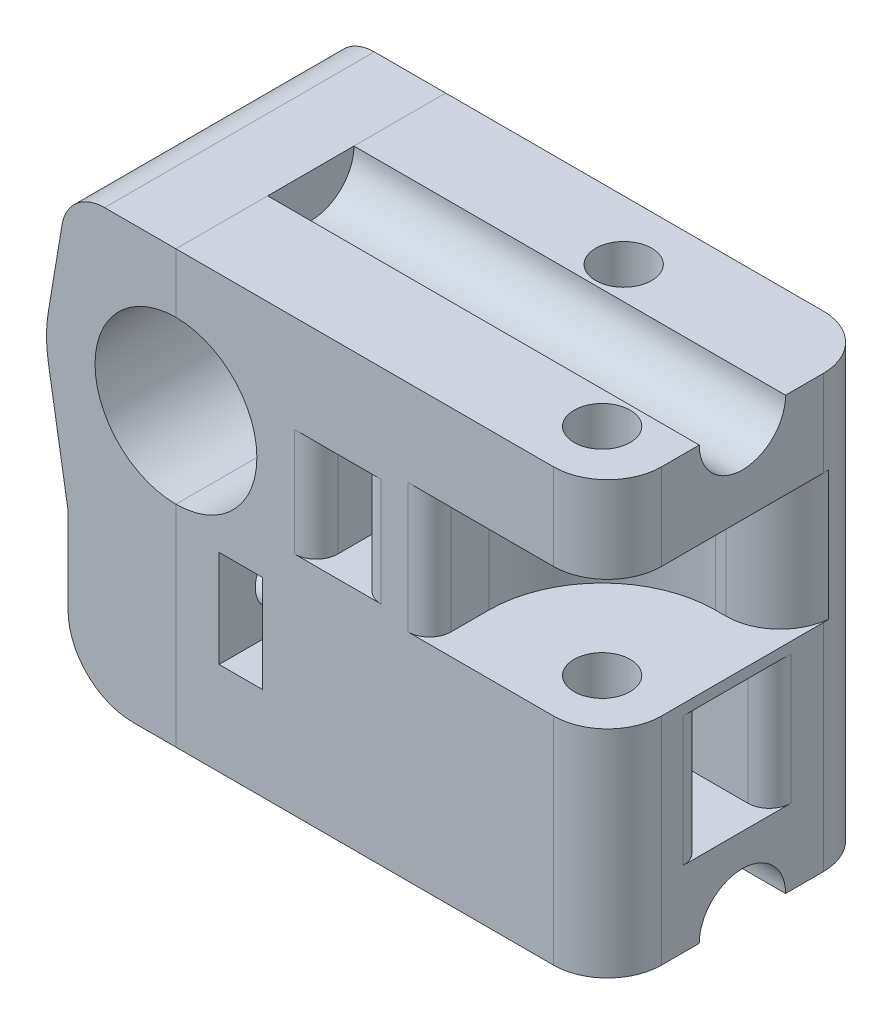
SolidWorks part; units mm, degrees
ref_plane "Front Plane" through (0, 0, 0) normal (0, 0, 1) x (1, 0, 0)
ref_plane "Top Plane" through (0, 0, 0) normal (0, 1, 0) x (1, 0, 0)
ref_plane "Right Plane" through (0, 0, 0) normal (1, 0, 0) x (0, 0, -1)
sketch "Sketch1" plane through (0, 0, 0) normal (0, 0, 1) x (1, 0, 0)
  line L0 (-15, 7) -> (-15, 0) construction
  line L1 (25, -20) -> (-25, -20)
  line L2 (25, -20) -> (25, 20)
  line L3 (25, 20) -> (-25, 20)
  line L4 (-25, -20) -> (-25, 20)
  line L5 (25, -20) -> (-25, 20) construction
  line L6 (25, 20) -> (-25, -20) construction
  line L7 (-15, 0) -> (0, 0) construction
  line L8 (-15, 7) -> (-15, -8) construction
  line L9 (-15, -8) -> (12.294, -8) construction
  line L10 (12.294, -8) -> (12.294, 8) construction
  line L11 (0, 0) -> (12.294, 0) construction
  circle A2 centre (-15, 7) radius 7.5
  point P0 (0, 0)
  dimension "D2" = 10
  dimension "D3" = 50
  dimension "D5" = 15
  dimension "D4" = 40
  dimension "D6" = 16
extrude "Boss-Extrude1" add sketch "Sketch1" along normal blind 25 contours A2 L3 L4 L1 L2 region at (1.4538, -0.6784, 0)
sketch "Sketch2" plane through (25, 0, 0) normal (1, 0, 0) x (0, 0, -1)
  line L0 (-25, 20) -> (0, -20) construction
  line L1 (-12.5, 20) -> (-12.5, -20) construction
  line L2 (-25, 20) -> (0, 20) construction
  circle A0 centre (-12.5, 20) radius 4
  circle A1 centre (-12.5, -20) radius 4
  point P7 (-12.5, 0)
  dimension "D2" = 8
extrude "Cut-Extrude1" cut sketch "Sketch2" against normal offset from surface (40 mm away) 10 up to face at (-25, 0, 12.5)
sketch "Sketch4" plane through (0, 20, 0) normal (0, 1, 0) x (1, 0, 0)
  line L0 (-15, -12.5) -> (13, -12.5) construction
  line L1 (19, -19.5) -> (7, -19.5) construction
  line L2 (19, -19.5) -> (19, -5.5) construction
  line L3 (19, -5.5) -> (7, -5.5) construction
  line L4 (7, -19.5) -> (7, -5.5) construction
  line L5 (19, -19.5) -> (7, -5.5) construction
  line L6 (19, -5.5) -> (7, -19.5) construction
  line L7 (-15, -8.5) -> (-15, -16.5) construction
  line L9 (-5.4237, 0) -> (-5.4237, -25)
  line L17 (-25, -25) -> (-25, 0) construction
  circle A0 centre (19, -19.5) radius 2.6
  circle A1 centre (7, -5.5) radius 2.6
  point P0 (13, -12.5)
  dimension "D3" = 5.2
  dimension "D1" = 12
  dimension "D2" = 14
  dimension "D4" = 32
extrude "Cut-Extrude2" cut sketch "Sketch4" against normal through all contours A1 | A0 region at (19, 20, 19.5) region at (7, 20, 5.5)
sketch "Sketch17" plane through (0, 0, 0) normal (0, 0, -1) x (-1, 0, 0)
  line L0 (25, -20) -> (25, 20) construction
  line L1 (25, 20) -> (26.8369, 8.9716)
  line L2 (25, -6) -> (26.8369, 5.0284)
  line L3 (25, 20) -> (25, -6)
  circle A0 centre (15, 7) radius 12
  point P3 (27, 7)
  line M12 (25, -20) -> (25, 20)
  dimension "D1" = 2
extrude "Boss-Extrude2" add sketch "Sketch17" against normal up to surface (25 mm away) contours A0 L2 M12 | A0 L3 | A0 L1 M12 region at (-25.5401, 14.7119, 0) region at (-25.806, 7, 0) region at (-25.5401, -0.7119, 0) up to face at (-7.5, 7, 25)
sketch "Sketch7" plane through (0, 20, 0) normal (0, 1, 0) x (1, 0, 0)
  line L0 (9, 14) -> (9, -25)
  line L2 (21, -39) -> (21, 0)
  point P6 (9, -5.5)
  point P12 (21, -19.5)
sketch "Sketch6" plane through (0, 0, 25) normal (0, 0, 1) x (1, 0, 0)
  line L0 (9.6, 20) -> (4.4, 20) construction
  line L1 (-2, 11) -> (2, 11)
  line L2 (-2, 11) -> (-2, 1)
  line L3 (-2, 1) -> (2, 1)
  line L4 (2, 11) -> (2, 1)
  line L5 (-2, 11) -> (2, 1) construction
  line L6 (-2, 1) -> (2, 11) construction
  point P0 (0, 6)
  point P5 (0, 0)
  point P6 (9, 20)
  dimension "D1" = 11
  dimension "D2" = 4
  dimension "D3" = 10
  dimension "D4" = 7
extrude "Cut-Extrude3" cut sketch "Sketch6" against normal through all
sketch "Sketch8" plane through (0, 20, 0) normal (0, 1, 0) x (1, 0, 0)
  line L0 (19, -9) -> (29.5, -9)
  line L1 (29.5, -9) -> (29.5, -30)
  line L2 (29.5, -30) -> (19, -30)
  line L3 (8.5, -19.5) -> (8.5, -30)
  line L4 (8.5, -30) -> (19, -30)
  arc A0 (19, -9) -> (8.5, -19.5) centre (19, -19.5) ccw
  dimension "D1" = 21
extrude "Cut-Extrude4" cut sketch "Sketch8" against normal blind 12 from offset 8 offset against normal yes
sketch "Sketch11" plane through (0, 20, 0) normal (0, 1, 0) x (1, 0, 0)
  line L1 (16, -5) -> (16, -10)
  line L2 (7, -16) -> (26.2266, -16)
  line L4 (16, -10) -> (26.2266, -10)
  line L5 (26.2266, -16) -> (26.2266, -10)
  line L7 (-3.5, -5.5) -> (-3.5, 3.5)
  line L8 (-3.5, 3.5) -> (16, 3.5)
  line L9 (16, -5) -> (16, 3.5)
  arc A0 (-3.5, -5.5) -> (7, -16) centre (7, -5.5) ccw
  dimension "D1" = 21
  dimension "D2" = 6
extrude "Cut-Extrude5" cut sketch "Sketch11" against normal blind 12 from offset 21 offset against normal yes
sketch "Sketch12" plane through (-25, 0, 0) normal (-1, 0, 0) x (0, 0, 1)
  line L0 (0, -20) -> (0, -6) construction
  line L1 (25, -20) -> (25, -6) construction
  line L2 (6, -6.8649) -> (19, -6.8649)
  circle A0 centre (19, -6.8649) radius 2.65
  circle A1 centre (6, -6.8649) radius 2.65
  dimension "D3" = 5.3
  dimension "D1" = 6
  dimension "D2" = 6
extrude "Cut-Extrude6" cut sketch "Sketch12" against normal blind 22 contours A0 | A1 | A1 | A0 region at (-25, -4.2899, 19) region at (-25, -6.8649, 3.425)
sketch "Sketch13" plane through (-25, 0, 0) normal (-1, 0, 0) x (0, 0, 1)
  line L2 (4.5292, -11.3649) -> (8.5981, -11.3649)
  line L3 (8.5981, -11.3649) -> (11.1962, -6.8649)
  line L4 (11.1962, -6.8649) -> (8.5981, -2.3649)
  line L5 (8.5981, -2.3649) -> (3.8195, -2.3649)
  line L8 (21.5981, -2.3649) -> (16.4019, -2.3649)
  line L9 (16.4019, -2.3649) -> (13.8038, -6.8649)
  line L10 (13.8038, -6.8649) -> (16.4019, -11.3649)
  line L11 (16.4019, -11.3649) -> (21.8459, -11.3649)
  line L13 (3.8195, -2.3649) -> (-1.875, -2.3649)
  line L15 (4.5292, -11.3649) -> (-1.875, -11.3649)
  line L16 (-1.875, -2.3649) -> (-1.875, -11.3649)
  line L17 (21.5981, -2.3649) -> (28.6026, -2.3649)
  line L19 (21.8459, -11.3649) -> (28.6026, -11.3649)
  line L20 (28.6026, -2.3649) -> (28.6026, -11.3649)
  line L21 (23.6325, -5.8887) -> (22.449, -3.8387) [skipped]
  line L22 (22.1617, -10.3887) -> (23.3453, -8.3387) [skipped]
  line L23 (2.1029, -4.6149) -> (0.9193, -6.6649) [skipped]
  line L24 (2.1029, -9.1149) -> (3.2865, -11.1649) [skipped]
  arc A0 (6.8963, -11.3649) -> (6.8963, -2.3649) centre (6, -6.8649) ccw construction
  arc A1 (19.2309, -2.3649) -> (18.7691, -11.3649) centre (19, -6.8649) ccw construction
  arc M5 (21.5049, -6) -> (16.4951, -6) centre (19, -6.8649) cw
  arc M6 (8.5049, -6) -> (3.4951, -6) centre (6, -6.8649) cw
  line M7 (0, -6) -> (0, -20)
  line M9 (25, -20) -> (25, -6)
  dimension "D1" = 9
extrude "Cut-Extrude7" cut sketch "Sketch13" against normal blind 4 from offset 14 contours L15 L2 L3 L4 L5 L13 M7 M6 | L11 L19 L17 L8 L9 L10 M9 M5 | M6 | M5 region at (-25, -6.8649, 4.0349) region at (-25, -6.8649, 21.8319) offset against normal yes
sketch "Sketch14" plane through (-25, 0, 0) normal (-1, 0, 0) x (0, 0, 1)
  circle A0 centre (6, -6.8649) radius 5.5
  circle A1 centre (19, -6.8649) radius 5.5
  dimension "D1" = 11
extrude "Cut-Extrude8" cut sketch "Sketch14" against normal blind 5 and the other way blind 10
sketch "Sketch15" plane through (0, 0, 0) normal (0, 0, -1) x (-1, 0, 0)
  line L0 (15, 7) -> (15, -0.5) construction
  circle A0 centre (15, 7) radius 7.5 construction
ref_plane "Plane1" through (-15, 0, 0) normal (-1, 0, 0) x (0, 0, 1)
sketch "Sketch18" plane through (0, 0, 25) normal (0, 0, 1) x (1, 0, 0)
  line L0 (-11, -20.7299) -> (-11, 7)
  line L2 (-15, 7) -> (-11, 7)
  line L3 (-15.0099, -20.7299) -> (-11, -20.7299)
  line L4 (-25, -7.7223) -> (-26.8453, -18.7493)
  line L7 (-15.0099, -32.7299) -> (-3.0099, -32.7299)
  line L8 (-3.0099, -32.7299) -> (0, -20)
  line L10 (-15, -20) -> (0, -20)
  line L11 (-25, -7.7223) -> (-15.0099, -8.7299)
  line L12 (-15.0099, -8.7299) -> (-15, -20)
  line L13 (-25, -6) -> (-26.8369, 5.0284) construction
  line L14 (25, -20) -> (-25, -20) construction
  line L15 (-3.0099, -20.7299) -> (-3.0099, -32.7299) construction
  circle A0 centre (-15.0099, -20.7299) radius 7.5
  circle A2 centre (-15.0099, -20.7299) radius 12
  arc A4 (-26.8369, 8.9716) -> (-26.8369, 5.0284) centre (-15, 7) ccw construction
  circle A5 centre (-15, 7) radius 7.5 construction
  point P4 (-11, -6.8649)
sketch "Sketch20" plane through (-20, 0, 0) normal (-1, 0, 0) x (0, 0, 1)
  circle A0 centre (19, -6.8649) radius 5.5
  circle A1 centre (6, -6.8649) radius 5.5
split "Split1" trim tools "Plane1" bodies to split 109 118 resulting bodies 110 111
fillet "Fillet1" radius 5 3 edges at (25, 0, 0) (25, -10, 25) (25, 16, 25)
fillet "Fillet2" radius 2 9 edges at (16, -7, 0) (-3.5, -7, 0) (25, -7, 16) (25, -7, 10) (-2, 6, 0) (2, 6, 0) (2, 6, 25) (-2, 6, 25) (8.5, 6, 25)
fillet "Fillet3" radius 4 1 edges at (-25, 20, 12.5)
fillet "Fillet4" radius 5 1 edges at (25, 6, 9)
fillet "Fillet5" radius 6 1 edges at (-25, -20, 12.5)
